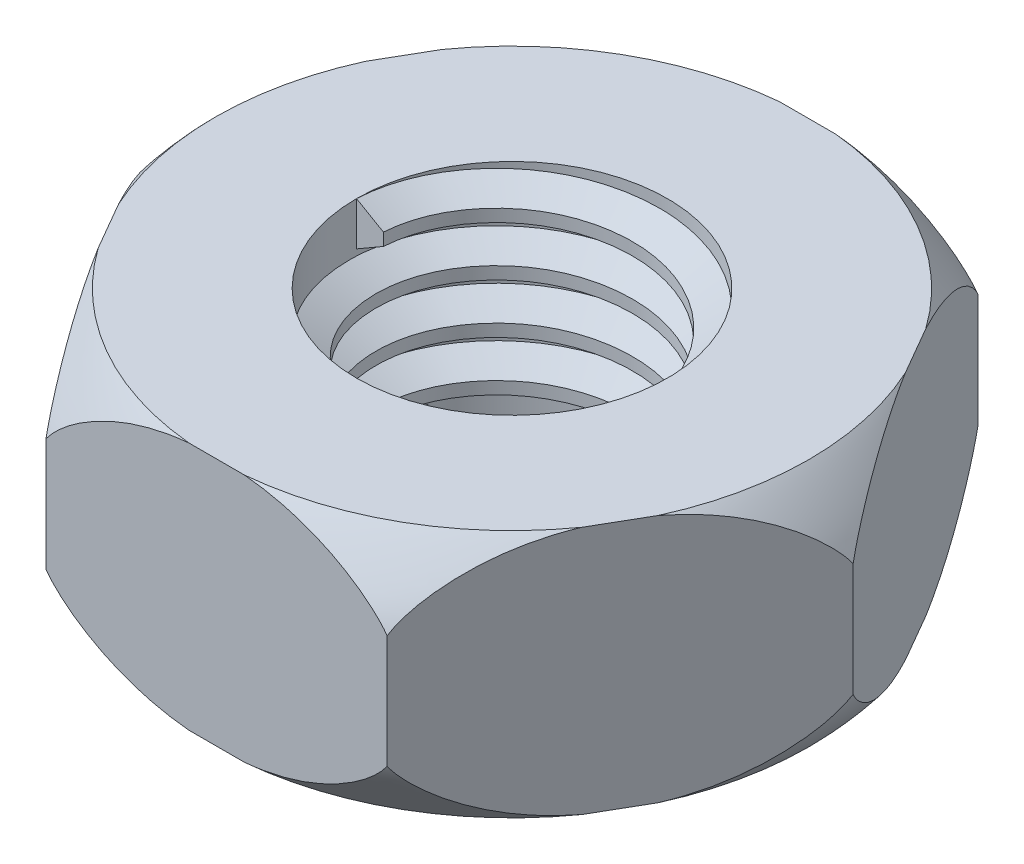
SolidWorks part; units mm, degrees
material "ASTM A36 Steel"
ref_plane "Front Plane" through (0, 0, 0) normal (0, 0, 1) x (1, 0, 0)
ref_plane "Top Plane" through (0, 0, 0) normal (0, 1, 0) x (1, 0, 0)
ref_plane "Right Plane" through (0, 0, 0) normal (1, 0, 0) x (0, 0, -1)
sketch "Sketch1" plane through (0, 0, 0) normal (0, 1, 0) x (1, 0, 0)
  line L1 (2.7424, -4.75) -> (5.4848, 0)
  line L2 (5.4848, 0) -> (2.7424, 4.75)
  line L3 (2.7424, 4.75) -> (-2.7424, 4.75)
  line L4 (-2.7424, 4.75) -> (-5.4848, 0)
  line L5 (-5.4848, 0) -> (-2.7424, -4.75)
  line L6 (-2.7424, -4.75) -> (2.7424, -4.75)
  circle A0 centre (0, 0) radius 4.75 construction
  circle A2 centre (0, 0) radius 6.5
  circle A3 centre (0, 0) radius 2.5
  point P12 (0, 0)
  dimension "D2" = 5
  dimension "D1" = 9.5
  dimension "D3" = 13
extrude "Boss-Extrude1" add sketch "Sketch1" against normal blind 2 contours L5 L6 L1 L2 L3 L4 A3
sketch "Sketch2" plane through (0, 0, 0) normal (0, 0, 1) x (1, 0, 0)
  line L1 (-5.4848, -0.9103) -> (-5.4848, -2)
  line L2 (-5.4848, -2) -> (-5.4848, 0) construction
  line L3 (-5.4848, -2) -> (-4.771, -2)
  line L4 (-5.4848, -2) -> (-2.7424, -2) construction
  line L6 (0, 0) -> (0, -3.8592) construction
  spline S0 degree 3 poles (-4.771, -2) (-4.9764, -1.7911) (-5.3423, -1.3056) (-5.4848, -0.9103) knots 0 0 0 0 0.941596 0.941596 0.941596 0.941596
  dimension "D1" = 1.0897
  dimension "D2" = 0.7138
revolve "Cut-Revolve1" cut sketch "Sketch2" angle 360 about L6
mirror "Mirror2" about plane through (0, 0, 0) normal (0, 1, 0) of "Boss-Extrude1", "Cut-Revolve1"
thread "Thread1" pitch 0.8 start angle 0, offset 0, length 0, pitch 0.8, diameter 5
ref_plane "Plane1" through (-2.5, 2, 0) normal (0, 0, 1) x (-1, 0, 0)
sketch "Thread Profile1" plane through (-2.5, 2, 0) normal (0, 0, 1) x (-1, 0, 0)
  line L0 (0, 0) -> (0, 0.8) construction
  line L11 (0, 0) -> (0, 0.7)
  line L12 (0, 0.7) -> (-0.433, 0.45)
  line L13 (-0.433, 0.45) -> (-0.433, 0.25)
  line L15 (-0.433, 0.25) -> (0, 0)
  line L17 (-0.433, 0.35) -> (0, 0.35) construction
  point P2 (0, 0)
  dimension "Pitch" = 0.8
  dimension "Profile_Angle" = 60
  dimension "Profile_Land" = 0.2
  dimension "Profile_Height" = 0.433
scale "Scale1" scale about centroid uniform scaling yes scale factor 0.6
